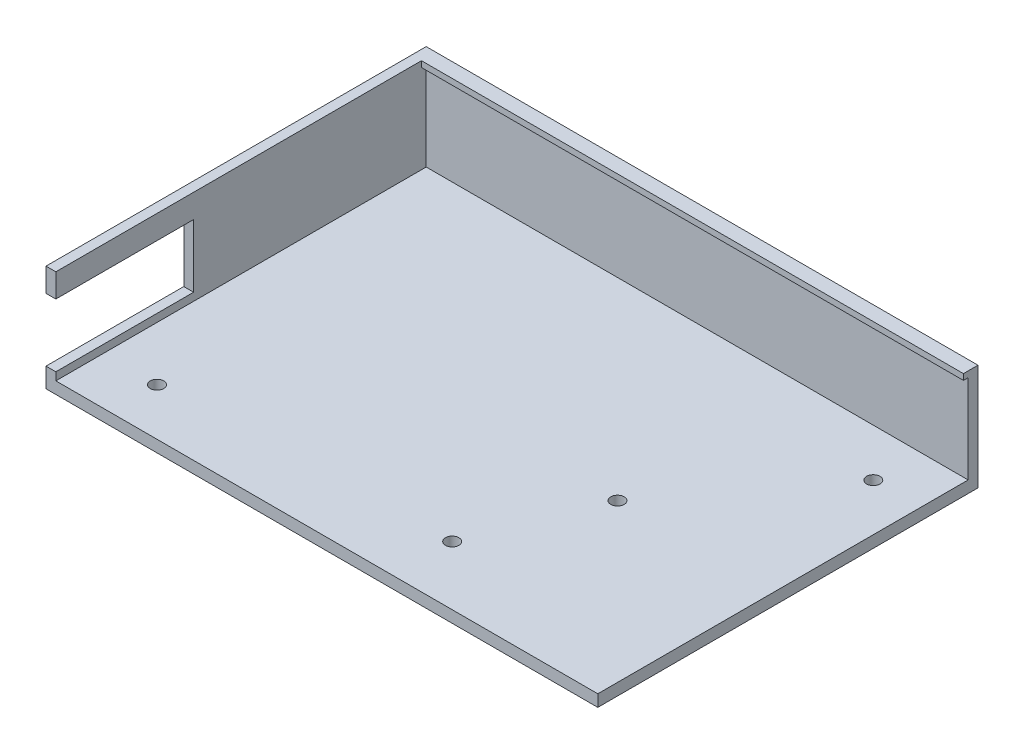
SolidWorks part; units mm, degrees
ref_plane "Front Plane" through (0, 0, 0) normal (0, 0, 1) x (1, 0, 0)
ref_plane "Top Plane" through (0, 0, 0) normal (0, 1, 0) x (1, 0, 0)
ref_plane "Right Plane" through (0, 0, 0) normal (1, 0, 0) x (0, 0, -1)
sketch "Sketch1" plane through (0, 0, 0) normal (0, 1, 0) x (1, 0, 0)
  line L1 (-140.2, -96.6) -> (140.2, -96.6)
  line L2 (-140.2, -96.6) -> (-140.2, 96.6)
  line L3 (-140.2, 96.6) -> (140.2, 96.6)
  line L4 (140.2, -96.6) -> (140.2, 96.6)
  line L5 (-140.2, -96.6) -> (140.2, 96.6) construction
  line L6 (-140.2, 96.6) -> (140.2, -96.6) construction
  point P0 (0, 0)
  dimension "D1" = 280.4
  dimension "D2" = 193.2
extrude "Shell Block" add sketch "Sketch1" along normal blind 27
ref_plane "Shell Front" through (0, 27, 0) normal (0, 1, 0) x (1, 0, 0)
sketch "Sketch2" plane through (0, 27, 0) normal (0, 1, 0) x (1, 0, 0)
  line L1 (-137.7, -92.9) -> (137.7, -92.9)
  line L2 (-137.7, -92.9) -> (-137.7, 92.9)
  line L3 (-137.7, 92.9) -> (137.7, 92.9)
  line L4 (137.7, -92.9) -> (137.7, 92.9)
  line L5 (-137.7, -92.9) -> (137.7, 92.9) construction
  line L6 (-137.7, 92.9) -> (137.7, -92.9) construction
  point P0 (0, 0)
  dimension "D1" = 275.4
  dimension "D2" = 185.8
extrude "Front Opening" cut sketch "Sketch2" against normal blind 1.5
ref_plane "Under Lip" through (0, 25.5, 0) normal (0, 1, 0) x (1, 0, 0)
sketch "Sketch3" plane through (0, 25.5, 0) normal (0, 1, 0) x (1, 0, 0)
  line L1 (-137.7, -94.1) -> (137.7, -94.1)
  line L2 (-137.7, -94.1) -> (-137.7, 94.1)
  line L3 (-137.7, 94.1) -> (137.7, 94.1)
  line L4 (137.7, -94.1) -> (137.7, 94.1)
  line L5 (-137.7, -94.1) -> (137.7, 94.1) construction
  line L6 (-137.7, 94.1) -> (137.7, -94.1) construction
  point P0 (0, 0)
  dimension "D1" = 275.4
  dimension "D2" = 188.2
extrude "Display Pocket" cut sketch "Sketch3" against normal blind 22.5
ref_plane "Back Inner" through (0, 3, 0) normal (0, 1, 0) x (1, 0, 0)
sketch "Sketch4" plane through (0, 3, 0) normal (0, 1, 0) x (1, 0, 0)
  line L1 (66, 28) -> (69, 28)
  line L2 (66, 28) -> (66, 84)
  line L3 (66, 84) -> (69, 84)
  line L4 (69, 28) -> (69, 84)
  line L6 (66, -84) -> (69, -84)
  line L7 (66, -84) -> (66, -28)
  line L8 (66, -28) -> (69, -28)
  line L9 (69, -84) -> (69, -28)
  line L11 (74, 28) -> (77, 28)
  line L12 (74, 28) -> (74, 84)
  line L13 (74, 84) -> (77, 84)
  line L14 (77, 28) -> (77, 84)
  line L16 (74, -84) -> (77, -84)
  line L17 (74, -84) -> (74, -28)
  line L18 (74, -28) -> (77, -28)
  line L19 (77, -84) -> (77, -28)
  line L21 (82, 28) -> (85, 28)
  line L22 (82, 28) -> (82, 84)
  line L23 (82, 84) -> (85, 84)
  line L24 (85, 28) -> (85, 84)
  line L26 (82, -84) -> (85, -84)
  line L27 (82, -84) -> (82, -28)
  line L28 (82, -28) -> (85, -28)
  line L29 (85, -84) -> (85, -28)
  line L31 (90, 28) -> (93, 28)
  line L32 (90, 28) -> (90, 84)
  line L33 (90, 84) -> (93, 84)
  line L34 (93, 28) -> (93, 84)
  line L36 (90, -84) -> (93, -84)
  line L37 (90, -84) -> (90, -28)
  line L38 (90, -28) -> (93, -28)
  line L39 (93, -84) -> (93, -28)
  line L41 (98, 28) -> (101, 28)
  line L42 (98, 28) -> (98, 84)
  line L43 (98, 84) -> (101, 84)
  line L44 (101, 28) -> (101, 84)
  line L46 (98, -84) -> (101, -84)
  line L47 (98, -84) -> (98, -28)
  line L48 (98, -28) -> (101, -28)
  line L49 (101, -84) -> (101, -28)
  line L51 (106, 28) -> (109, 28)
  line L52 (106, 28) -> (106, 84)
  line L53 (106, 84) -> (109, 84)
  line L54 (109, 28) -> (109, 84)
  line L56 (106, -84) -> (109, -84)
  line L57 (106, -84) -> (106, -28)
  line L58 (106, -28) -> (109, -28)
  line L59 (109, -84) -> (109, -28)
  line L61 (114, 28) -> (117, 28)
  line L62 (114, 28) -> (114, 84)
  line L63 (114, 84) -> (117, 84)
  line L64 (117, 28) -> (117, 84)
  line L66 (114, -84) -> (117, -84)
  line L67 (114, -84) -> (114, -28)
  line L68 (114, -28) -> (117, -28)
  line L69 (117, -84) -> (117, -28)
  line L71 (122, 28) -> (125, 28)
  line L72 (122, 28) -> (122, 84)
  line L73 (122, 84) -> (125, 84)
  line L74 (125, 28) -> (125, 84)
  line L76 (122, -84) -> (125, -84)
  line L77 (122, -84) -> (122, -28)
  line L78 (122, -28) -> (125, -28)
  line L79 (125, -84) -> (125, -28)
extrude "Vent Slots" cut sketch "Sketch4" against normal blind 4
sketch "Sketch5" plane through (0, 0, 0) normal (1, 0, 0) x (0, 0, -1)
  line L1 (-35, 5) -> (35, 5)
  line L2 (-35, 5) -> (-35, 21)
  line L3 (-35, 21) -> (35, 21)
  line L4 (35, 5) -> (35, 21)
extrude "Cable Exit (+X short side)" cut sketch "Sketch5" against normal blind 141.2
sketch "Sketch6" plane through (0, 3, 0) normal (0, 1, 0) x (1, 0, 0)
  circle A0 centre (-40, -45) radius 1.7
  circle A1 centre (-40, 45) radius 1.7
  circle A2 centre (40, -45) radius 1.7
  circle A3 centre (40, 45) radius 1.7
  circle A4 centre (-52, -15) radius 1.7
  circle A5 centre (-52, 15) radius 1.7
  circle A6 centre (52, -15) radius 1.7
  circle A7 centre (52, 15) radius 1.7
  circle A8 centre (-12, -82) radius 1.7
  circle A9 centre (-12, 82) radius 1.7
  circle A10 centre (12, -82) radius 1.7
  circle A11 centre (12, 82) radius 1.7
  circle A12 centre (-124, -12) radius 1.7
  circle A13 centre (-124, 12) radius 1.7
  circle A14 centre (124, -12) radius 1.7
  circle A15 centre (124, 12) radius 1.7
extrude "Bolt Holes" cut sketch "Sketch6" against normal blind 4
sketch "Sketch7" plane through (0, 0, 0) normal (0, 1, 0) x (1, 0, 0)
  line L1 (200, -200) -> (0, -200)
  line L2 (200, -200) -> (200, 200)
  line L3 (200, 200) -> (0, 200)
  line L4 (0, -200) -> (0, 200)
extrude "Keep one half (X)" cut sketch "Sketch7" against normal through all and the other way through all
sketch "Sketch8" plane through (0, 0, 0) normal (0, 1, 0) x (1, 0, 0)
  line L1 (-200, 0) -> (200, 0)
  line L2 (-200, 0) -> (-200, -200)
  line L3 (-200, -200) -> (200, -200)
  line L4 (200, 0) -> (200, -200)
extrude "Keep one quarter (Z)" cut sketch "Sketch8" against normal through all and the other way through all
equation "\"DispL\"= 274.2"
equation "\"DispW\"= 187.0"
equation "\"DispT\"= 20.0"
equation "\"Clr\"= 0.6"
equation "\"Wall\"= 2.5"
equation "\"BackT\"= 3.0"
equation "\"CableRoom\"= 4.0"
equation "\"LipW\"= 1.2"
equation "\"LipT\"= 1.5"
equation "\"CableW\"= 70.0"
equation "\"CableH\"= 16.0"
equation "\"BoltD\"= 3.4"
equation "\"ShellL\"= \"DispL\" + 2 * \"Clr\" + 2 * \"Wall\""
equation "\"ShellW\"= \"DispW\" + 2 * \"Clr\" + 2 * \"Wall\""
equation "\"ShellH\"= \"BackT\" + \"DispT\" + \"CableRoom\""
equation "\"D1@Sketch1\" = \"ShellL\""
equation "\"D2@Sketch1\" = \"ShellW\""
equation "\"D1@Shell Block\" = \"ShellH\""
equation "\"D1@Shell Front\" = \"ShellH\""
equation "\"D1@Sketch2\" = \"DispL\" + 2 * \"Clr\""
equation "\"D2@Sketch2\" = \"DispW\" + 2 * \"Clr\" - 2 * \"LipW\""
equation "\"D1@Front Opening\" = \"LipT\""
equation "\"D1@Under Lip\" = \"ShellH\" - \"LipT\""
equation "\"D1@Sketch3\" = \"DispL\" + 2 * \"Clr\""
equation "\"D2@Sketch3\" = \"DispW\" + 2 * \"Clr\""
equation "\"D1@Display Pocket\" = \"ShellH\" - \"LipT\" - \"BackT\""
equation "\"D1@Back Inner\" = \"BackT\""
